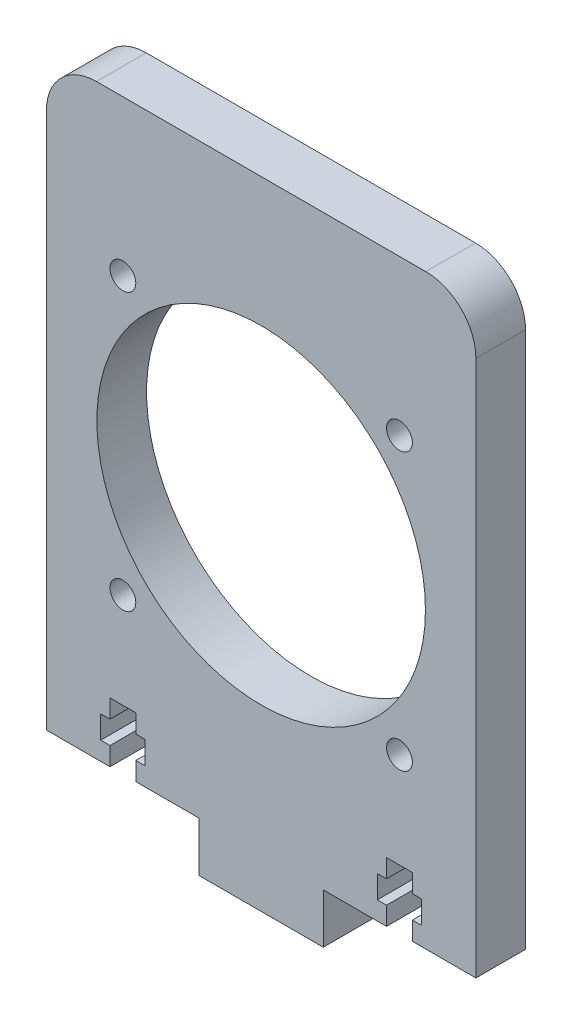
SolidWorks part; units mm, degrees
ref_plane "Front Plane" through (0, 0, 0) normal (0, 0, 1) x (1, 0, 0)
ref_plane "Top Plane" through (0, 0, 0) normal (0, 1, 0) x (1, 0, 0)
ref_plane "Right Plane" through (0, 0, 0) normal (1, 0, 0) x (0, 0, -1)
sketch "Sketch1" plane through (0, 0, 0) normal (0, 0, 1) x (1, 0, 0)
  line L0 (0, 0) -> (-35.3553, 35.3553) construction
  line L1 (-54.9, 75) -> (54.9, 75)
  line L2 (-54.9, 75) -> (-54.9, -75)
  line L3 (-54.9, -75) -> (54.9, -75)
  line L4 (54.9, 75) -> (54.9, -75)
  line L7 (-54.9, 0) -> (54.9, 0) construction
  line L8 (0, 75) -> (0, -75) construction
  circle A0 centre (0, 0) radius 42
  circle A1 centre (-35.3553, 35.3553) radius 3.3
  circle A2 centre (35.3553, 35.3553) radius 3.3
  circle A3 centre (35.3553, -35.3553) radius 3.3
  circle A4 centre (-35.3553, -35.3553) radius 3.3
  dimension "D1" = 84
  dimension "D5" = 6.6
  dimension "D7" = 50
  dimension "D8" = 50
  dimension "D2" = 109.8
  dimension "D3" = 150
  dimension "D4" = 45
  dimension "D6" = 50
extrude "Boss-Extrude1" add sketch "Sketch1" along normal blind 12.7 contours L4 L1 L2 L3 A2 A1 A0 A3 A4 region at (0, 73.1411, 0)
sketch "Sketch2" plane through (0, 0, 0) normal (0, 0, -1) x (-1, 0, 0)
  line L0 (0, -75) -> (32.05, -75)
  line L1 (54.9, -75) -> (-54.9, -75) construction
  line L2 (32.05, -75) -> (32.05, -70.3)
  line L3 (32.05, -70.3) -> (29.686, -70.3)
  line L4 (29.686, -70.3) -> (29.686, -64.46)
  line L5 (29.686, -64.46) -> (32.05, -64.46)
  line L6 (32.05, -64.46) -> (32.05, -59.76)
  line L7 (32.05, -59.76) -> (38.65, -59.76)
  line L8 (38.65, -59.76) -> (38.65, -64.46)
  line L9 (38.65, -64.46) -> (41.014, -64.46)
  line L10 (41.014, -64.46) -> (41.014, -70.3)
  line L11 (41.014, -70.3) -> (38.65, -70.3)
  line L12 (38.65, -70.3) -> (38.65, -75)
  line L13 (38.65, -75) -> (32.05, -75)
  line L14 (0, -75) -> (0, 0) construction
  line L15 (-38.65, -75) -> (-32.05, -75)
  line L16 (-38.65, -70.3) -> (-38.65, -75)
  line L17 (-41.014, -70.3) -> (-38.65, -70.3)
  line L18 (-41.014, -64.46) -> (-41.014, -70.3)
  line L19 (-38.65, -64.46) -> (-41.014, -64.46)
  line L20 (-38.65, -59.76) -> (-38.65, -64.46)
  line L21 (-32.05, -59.76) -> (-38.65, -59.76)
  line L22 (-32.05, -64.46) -> (-32.05, -59.76)
  line L23 (-29.686, -64.46) -> (-32.05, -64.46)
  line L24 (-29.686, -70.3) -> (-29.686, -64.46)
  line L25 (-32.05, -70.3) -> (-29.686, -70.3)
  line L26 (-32.05, -75) -> (-32.05, -70.3)
  line M18 (-54.9, -75) -> (54.9, -75)
  dimension "D1" = 32.05
  dimension "D2" = 5.84
  dimension "D3" = 6.6
  dimension "D4" = 15.24
  dimension "D5" = 11.328
extrude "Cut-Extrude1" cut sketch "Sketch2" against normal through all contours L26 L25 L24 L23 L22 L21 L20 L19 L18 L17 L16 M18 | L2 L3 L4 L5 L6 L7 L8 L9 L10 L11 L12 L13 region at (35.35, -67.38, 0)
sketch "Sketch4" plane through (0, -75, 0) normal (0, -1, 0) x (1, 0, 0)
  line L0 (0, 0) -> (15.875, 0)
  line L1 (-32.05, 0) -> (32.05, 0) construction
  line L2 (15.875, 0) -> (15.875, 12.7)
  line L3 (-32.05, 12.7) -> (32.05, 12.7) construction
  line L4 (15.875, 12.7) -> (-15.875, 12.7)
  line L7 (0, 0) -> (-15.875, 0)
  line L8 (-15.875, 0) -> (-15.875, 12.7)
  dimension "D1" = 31.75
extrude "Boss-Extrude2" add sketch "Sketch4" along normal blind 12.7
fillet "Fillet1" radius 12.8 2 edges at (-54.9, 75, 6.35) (54.9, 75, 6.35)
